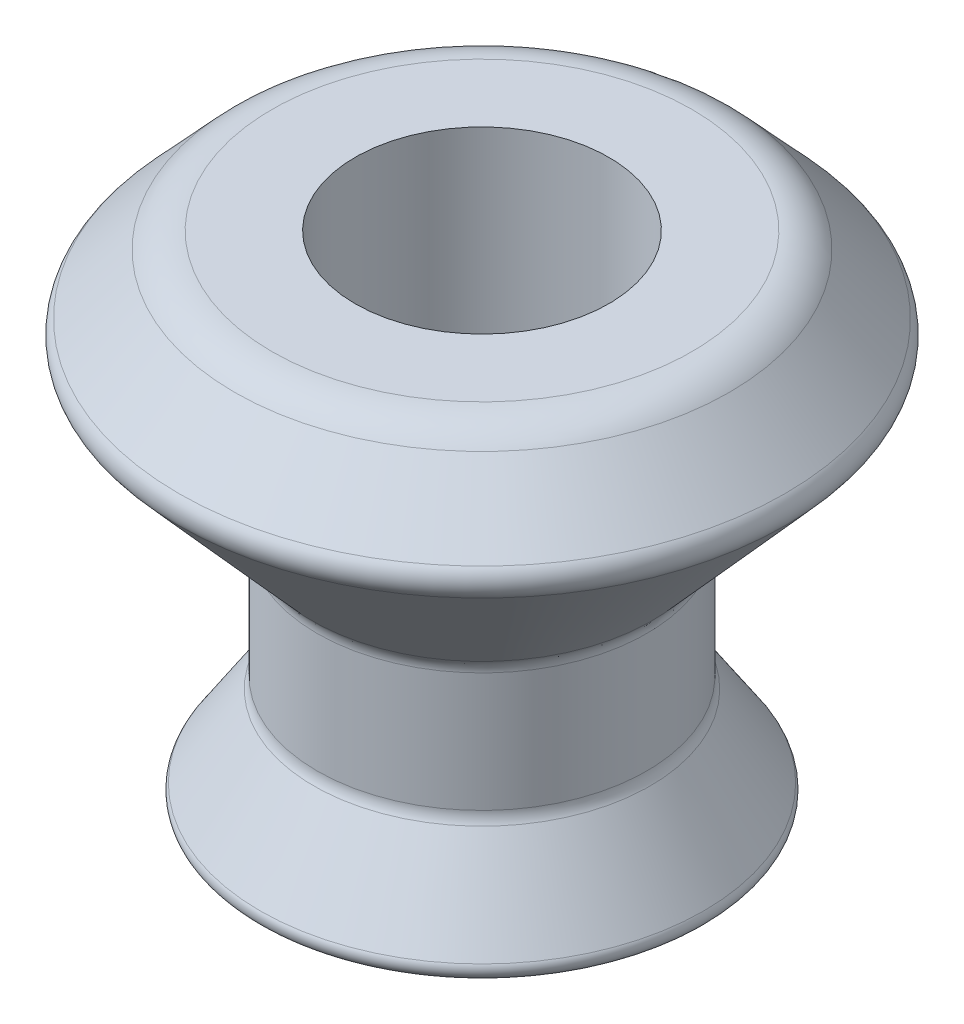
SolidWorks part; units mm, degrees
material "Chrome Stainless Steel"
ref_plane "Front Plane" through (0, 0, 0) normal (0, 0, 1) x (1, 0, 0)
ref_plane "Top Plane" through (0, 0, 0) normal (0, 1, 0) x (1, 0, 0)
ref_plane "Right Plane" through (0, 0, 0) normal (1, 0, 0) x (0, 0, -1)
sketch "Sketch1" plane through (0, 0, 0) normal (0, 0, 1) x (1, 0, 0)
  line L0 (0, 0) -> (5.2938, 0)
  line L1 (0, 0) -> (0, 12.2682)
  line L2 (0, 12.2682) -> (5.211, 12.2682)
  line L3 (0, 10.033) -> (7.8359, 10.033) construction
  line L4 (0, 2.54) -> (4.0894, 2.54) construction
  line L5 (0, 5.842) -> (4.0894, 5.842) construction
  line L6 (5.5058, 0.3939) -> (4.1734, 2.4127)
  line L7 (4.0894, 2.6925) -> (4.0894, 5.648)
  line L8 (4.2187, 5.9866) -> (7.5278, 9.6884)
  line L9 (7.5218, 10.3721) -> (6.1428, 11.8612)
  arc A0 (4.1734, 2.4127) -> (4.0894, 2.6925) centre (4.5974, 2.6925) cw
  arc A1 (4.0894, 5.648) -> (4.2187, 5.9866) centre (4.5974, 5.648) cw
  arc A2 (7.5278, 9.6884) -> (7.5218, 10.3721) centre (7.1491, 10.027) ccw
  arc A3 (5.2938, 0) -> (5.5058, 0.3939) centre (5.2938, 0.254) ccw
  arc A4 (5.211, 12.2682) -> (6.1428, 11.8612) centre (5.211, 10.9982) cw
  dimension "D5" = 0.508
  dimension "D6" = 0.254
  dimension "D7" = 1.27
  dimension "D1" = 10.033
  dimension "D2" = 2.54
  dimension "D3" = 5.842
  dimension "D4" = 12.2682
revolve "Revolve1" add sketch "Sketch1" angle 360 about L1
sketch "Sketch2" plane through (0, 12.2682, 0) normal (0, 1, 0) x (1, 0, 0)
  circle A0 centre (0, 0) radius 3.1496
  circle A1 centre (0, 0) radius 2.0066
extrude "Cut-Extrude1" cut sketch "Sketch2" against normal blind 9.652
extrude "Cut-Extrude2" cut sketch "Sketch2<2>" against normal through all contours A1 region at (0, 12.2682, 0)
sketch "Sketch2<2>" plane through (0, 12.2682, 0) normal (0, 1, 0) x (1, 0, 0) same geometry as "Sketch2"
